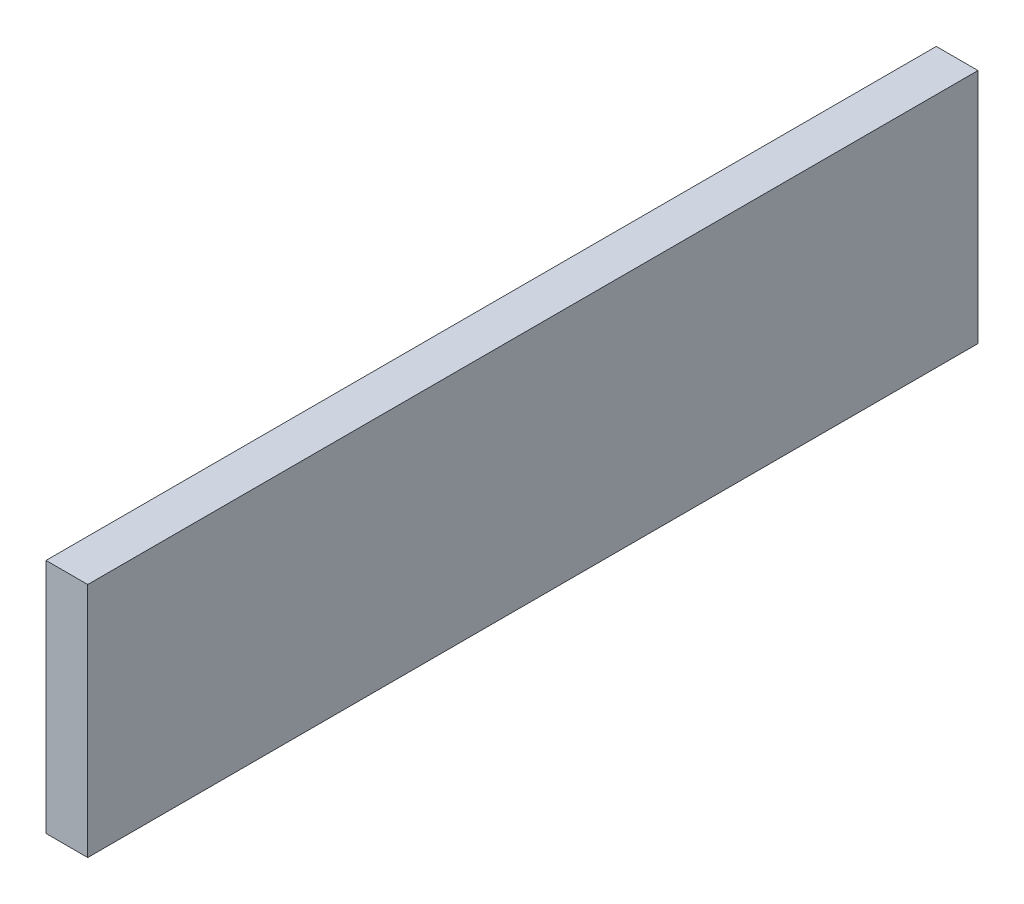
SolidWorks part; units mm, degrees
ref_plane "Plano frontal" through (0, 0, 0) normal (0, 0, 1) x (1, 0, 0)
ref_plane "Plano superior" through (0, 0, 0) normal (0, 1, 0) x (1, 0, 0)
ref_plane "Plano direito" through (0, 0, 0) normal (1, 0, 0) x (0, 0, -1)
sketch "Esboço1" plane through (0, 0, 0) normal (1, 0, 0) x (0, 0, -1)
  line L1 (-160, 42.5) -> (160, 42.5)
  line L2 (-160, 42.5) -> (-160, -42.5)
  line L3 (-160, -42.5) -> (160, -42.5)
  line L4 (160, 42.5) -> (160, -42.5)
  line L5 (-160, 42.5) -> (160, -42.5) construction
  line L6 (-160, -42.5) -> (160, 42.5) construction
  point P0 (0, 0)
  dimension "D1" = 320
  dimension "D2" = 85
extrude "Ressalto-extrusão1" add sketch "Esboço1" along normal blind 15
